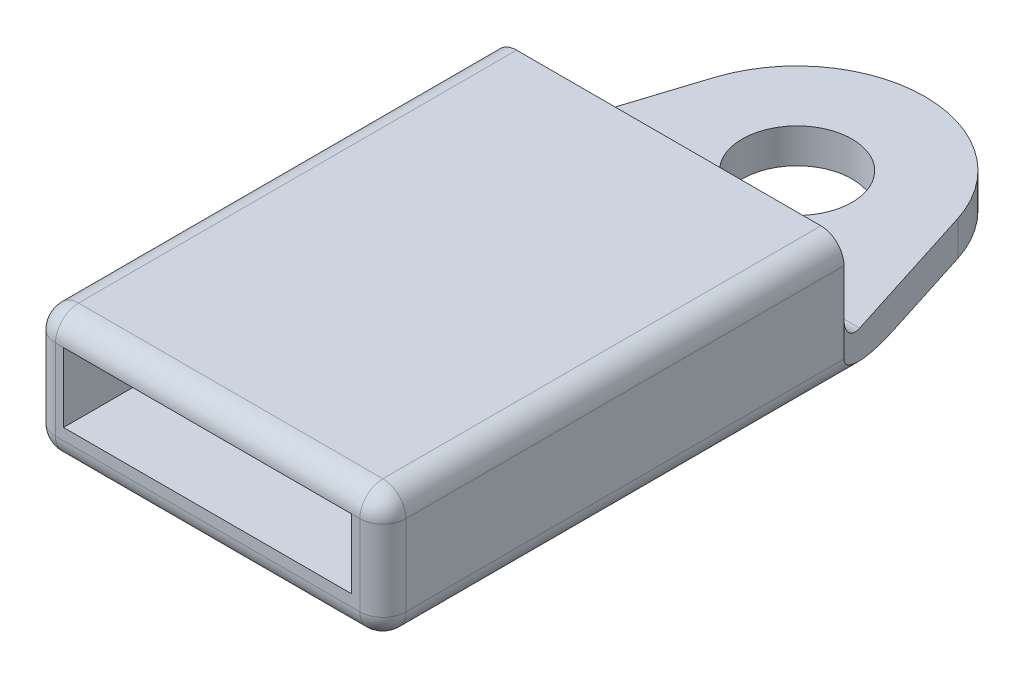
SolidWorks part; units mm, degrees
ref_plane "Front Plane" through (0, 0, 0) normal (0, 0, 1) x (1, 0, 0)
ref_plane "Top Plane" through (0, 0, 0) normal (0, 1, 0) x (1, 0, 0)
ref_plane "Right Plane" through (0, 0, 0) normal (1, 0, 0) x (0, 0, -1)
sketch "Sketch1" plane through (0, 0, 0) normal (0, 1, 0) x (1, 0, 0)
  line L1 (0, 0) -> (-30.4, 0)
  line L2 (0, 0) -> (0, 40)
  line L3 (0, 40) -> (-30.4, 40)
  line L4 (-30.4, 0) -> (-30.4, 40)
  line L5 (-27.7, 40) -> (-2.7, 40)
  line L6 (-27.7, 40) -> (-27.7, 0)
  line L7 (-27.7, 0) -> (-2.7, 0)
  line L8 (-2.7, 40) -> (-2.7, 0)
  line L9 (0, 0) -> (-2.7, 0)
  line L10 (0, 0) -> (0, 40)
  line L11 (0, 40) -> (-2.7, 40)
  line L12 (-2.7, 0) -> (-2.7, 40)
  line L13 (-30.4, 40) -> (-27.7, 40)
  line L14 (-30.4, 40) -> (-30.4, 0)
  line L15 (-30.4, 0) -> (-27.7, 0)
  line L16 (-27.7, 40) -> (-27.7, 0)
  dimension "D1" = 40
  dimension "D2" = 30.4
  dimension "D3" = 2.7
  dimension "D4" = 2.7
extrude "Boss-Extrude2" add sketch "Sketch1" along normal blind 11 contours L6 L3 L4 L1 | L3 L8 L1 L2 region at (-1.35, 0, -20) region at (-29.05, 0, -20)
sketch "Sketch3" plane through (0, 0, 0) normal (0, 1, 0) x (1, 0, 0)
  line L1 (-27.7, 40) -> (-2.7, 40)
  line L2 (-27.7, 40) -> (-27.7, 0)
  line L3 (-27.7, 0) -> (-2.7, 0)
  line L4 (-2.7, 40) -> (-2.7, 0)
extrude "Boss-Extrude3" add sketch "Sketch3" along normal blind 3
sketch "Sketch4" plane through (-27.7, 0, 0) normal (1, 0, 0) x (0, 0, -1)
  line L0 (40, 11) -> (40, 3) construction
  line L1 (40, 9) -> (0, 9)
  line L2 (40, 9) -> (40, 11)
  line L3 (40, 11) -> (0, 11)
  line L4 (0, 9) -> (0, 11)
  dimension "D1" = 2
extrude "Boss-Extrude4" add sketch "Sketch4" along normal up to next
sketch "Sketch5" plane through (0, 0, -40) normal (0, 0, -1) x (-1, 0, 0)
  line L0 (2.7, 3) -> (27.7, 3) construction
  line L1 (30.4, 0) -> (0, 0)
  line L2 (30.4, 0) -> (30.4, 3)
  line L3 (30.4, 3) -> (0, 3)
  line L4 (0, 0) -> (0, 3)
  dimension "D1" = 30.4
extrude "Boss-Extrude5" add sketch "Sketch5" along normal blind 22.225
sketch "Sketch6" plane through (0, 3, 0) normal (0, 1, 0) x (1, 0, 0)
  line L0 (-15.1159, 61.8095) -> (-15.5529, 0) construction
  line L1 (-30.4, 51.1125) -> (0, 51.1125) construction
  line L2 (-30.4, 62.225) -> (-30.4, 40) construction
  line L3 (0, 62.225) -> (0, 40) construction
  line L4 (-25.7602, 54.5723) -> (-30.4, 40)
  line L5 (0, 40) -> (-4.6112, 54.4837)
  arc A1 (-4.6112, 54.4837) -> (-25.7602, 54.5723) centre (-15.2, 51.1125) ccw
  dimension "D1" = 11.1125
extrude "Cut-Extrude1" cut sketch "Sketch6" against normal through all and the other way through all flip side to cut
sketch "Sketch7" plane through (0, 3, 0) normal (0, 1, 0) x (1, 0, 0)
  line L0 (-15.1534, 62.2249) -> (-15.2, 40) construction
  line L1 (0, 40) -> (-30.4, 40) construction
  line L2 (-26.3125, 51.1124) -> (-4.0875, 51.1124) construction
  arc A0 (-4.6112, 54.4837) -> (-25.7602, 54.5723) centre (-15.2, 51.1125) ccw construction
  circle A1 centre (-15.1767, 51.1125) radius 4.7625
  dimension "D1" = 11.1125
extrude "Cut-Extrude2" cut sketch "Sketch7" against normal through all
fillet "Fillet6" radius 2 1 edges at (-15.2, 11, 0)
fillet "Fillet8" radius 2 6 edges at (0, 4.5, 0) (0, 10.4142, -0.5858) (-30.4, 4.5, 0) (-30.4, 10.4142, -0.5858) (0, 11, -21) (-30.4, 11, -21)
fillet "Fillet9" radius 2 5 edges at (0, 0, -21) (-0.5858, 0, -0.5858) (-15.2, 0, 0) (-29.8142, 0, -0.5858) (-30.4, 0, -21)
fillet "Fillet10" radius 2 2 edges
